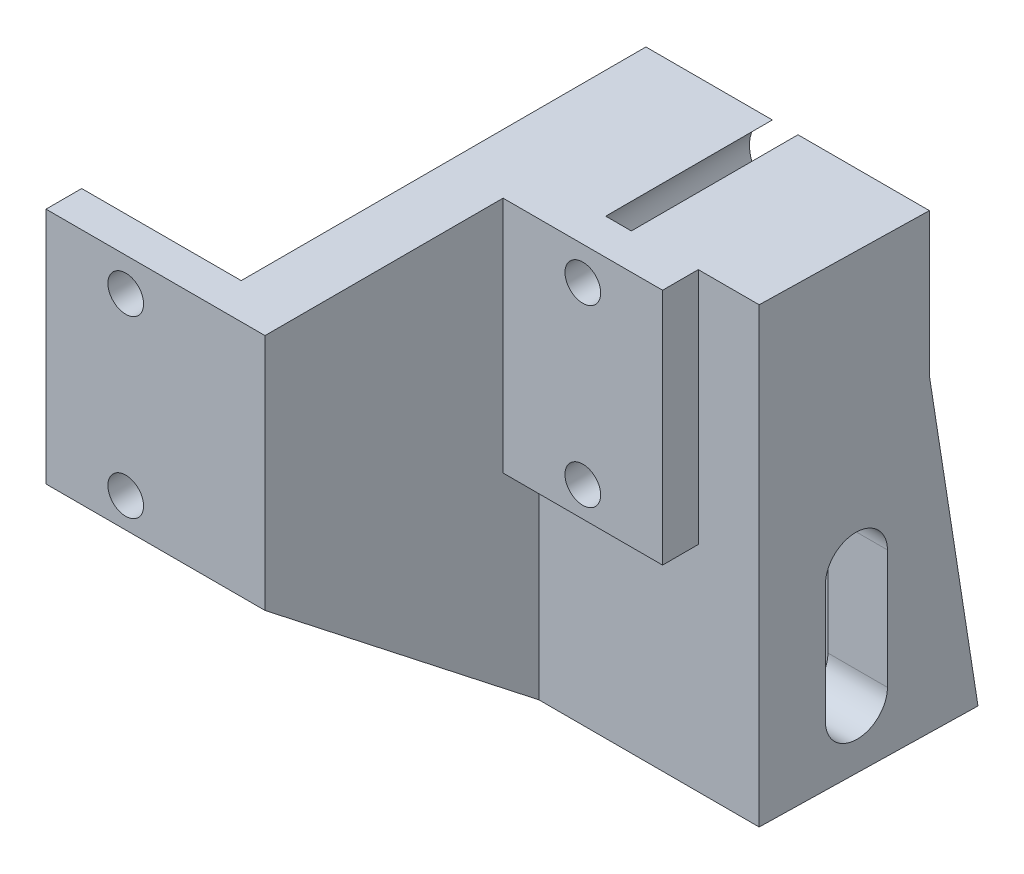
SolidWorks part; units mm, degrees
ref_plane "Front Plane" through (0, 0, 0) normal (0, 0, 1) x (1, 0, 0)
ref_plane "Top Plane" through (0, 0, 0) normal (0, 1, 0) x (1, 0, 0)
ref_plane "Right Plane" through (0, 0, 0) normal (1, 0, 0) x (0, 0, -1)
sketch "Sketch1" plane through (0, 0, 0) normal (0, 1, 0) x (1, 0, 0)
  line L0 (0, 0) -> (18.4, 0)
  line L1 (18.4, 0) -> (18.4, 20)
  line L2 (18.4, 20) -> (31.8, 20)
  line L3 (31.8, 20) -> (31.8, 23)
  line L4 (31.8, 23) -> (13.4, 23)
  line L5 (13.4, 23) -> (13.4, 3)
  line L6 (13.4, 3) -> (0, 3)
  line L7 (0, 3) -> (0, 0)
  dimension "D1" = 13.4
  dimension "D2" = 5
  dimension "D3" = 3
  dimension "D4" = 17
extrude "Boss-Extrude1" add sketch "Sketch1" along normal blind 20
sketch "Sketch2" plane through (0, 0, -20) normal (0, 0, 1) x (1, 0, 0)
  line L0 (25.1, 20) -> (25.1, 0) construction
  line L2 (31.8, 0) -> (13.4, 0) construction
  line L3 (18.4, 20) -> (31.8, 20) construction
  line L4 (18.4, 0) -> (31.8, 0) construction
  circle A0 centre (25.1, 2.5) radius 1.5
  circle A1 centre (25.1, 17.2) radius 1.5
  dimension "D1" = 3
  dimension "D2" = 2.5
  dimension "D3" = 14.7
extrude "Cut-Extrude1" cut sketch "Sketch2" against normal through all both and the other way through all
ref_plane "Plane1" through (15.9, 0, 0) normal (-1, 0, 0) x (0, 0, 1)
mirror "Mirror1" about plane through (15.9, 0, 0) normal (-1, 0, 0) of "Cut-Extrude1"
sketch "Sketch3" plane through (13.4, 0, 0) normal (-1, 0, 0) x (0, 0, 1)
  line L0 (-23, 0) -> (-23, -18)
  line L1 (-23, -18) -> (-41, -18)
  line L2 (-41, -18) -> (-37, 8)
  line L3 (-37, 8) -> (-37, 20)
  line L4 (-37, 20) -> (-23, 20)
  line L5 (-23, 20) -> (-23, 0)
  line L6 (-23, 0) -> (-3, 0) construction
  line L7 (-31, -13) -> (-31, -3) construction
  line L8 (-33.55, -13) -> (-33.55, -3)
  line L9 (-28.45, -13) -> (-28.45, -3)
  arc A0 (-33.55, -13) -> (-28.45, -13) centre (-31, -13) ccw
  arc A1 (-28.45, -3) -> (-33.55, -3) centre (-31, -3) ccw
  point P12 (-31, -8)
  dimension "D1" = 18
  dimension "D2" = 14
  dimension "D3" = 12
  dimension "D4" = 18
  dimension "D5" = 5.1
  dimension "D6" = 10
  dimension "D7" = 5
  dimension "D8" = 8
extrude "Boss-Extrude2" add sketch "Sketch3" against normal offset from surface (23.9 mm away) 5.5 up to face at (31.8, 10, -21.5) offset beyond the face yes
sketch "Sketch4" plane through (0, 0, -23) normal (0, 0, 1) x (1, 0, 0)
  circle A0 centre (25.1, 2.5) radius 3
  circle A1 centre (25.1, 17.2) radius 3
  dimension "D1" = 6
extrude "Cut-Extrude2" cut sketch "Sketch4" against normal through all
sketch "Sketch5" plane through (13.4, 0, 0) normal (-1, 0, 0) x (0, 0, 1)
  line L0 (0, 0) -> (-23, -18)
  line L1 (-23, -18) -> (-23, 0)
  line L2 (-23, 0) -> (0, 0)
extrude "Boss-Extrude3" add sketch "Sketch5" against normal up to surface (5 mm away) up to face at (18.4, 10, -10)
sketch "Sketch8" plane through (0, -18, 0) normal (0, -1, 0) x (1, 0, 0)
  line L0 (37.3, -41) -> (36.9167, -23)
  line L1 (37.3, -23) -> (18.4, -23) construction
  line L2 (36.9167, -23) -> (37.3, -23)
  line L3 (37.3, -23) -> (37.3, -41)
  dimension "D1" = 1.22
extrude "Cut-Extrude3" cut sketch "Sketch8" against normal through all
sketch "Sketch9" plane through (13.4, 0, 0) normal (-1, 0, 0) x (0, 0, 1)
  line L0 (-37, -3) -> (-37, -18)
  line L3 (-25, -3) -> (-25, -18)
  line L4 (-41, -18) -> (-23, -18) construction
  line L5 (-37, -18) -> (-25, -18)
  arc A4 (-37, -3) -> (-25, -3) centre (-31, -3) cw
  arc A5 (-28.45, -3) -> (-33.55, -3) centre (-31, -3) ccw construction
  dimension "D1" = 6
extrude "Cut-Extrude4" cut sketch "Sketch9" against normal offset from surface (18.8137 mm away) 5 up to face at (37.1126, 2.4, -32.2)
